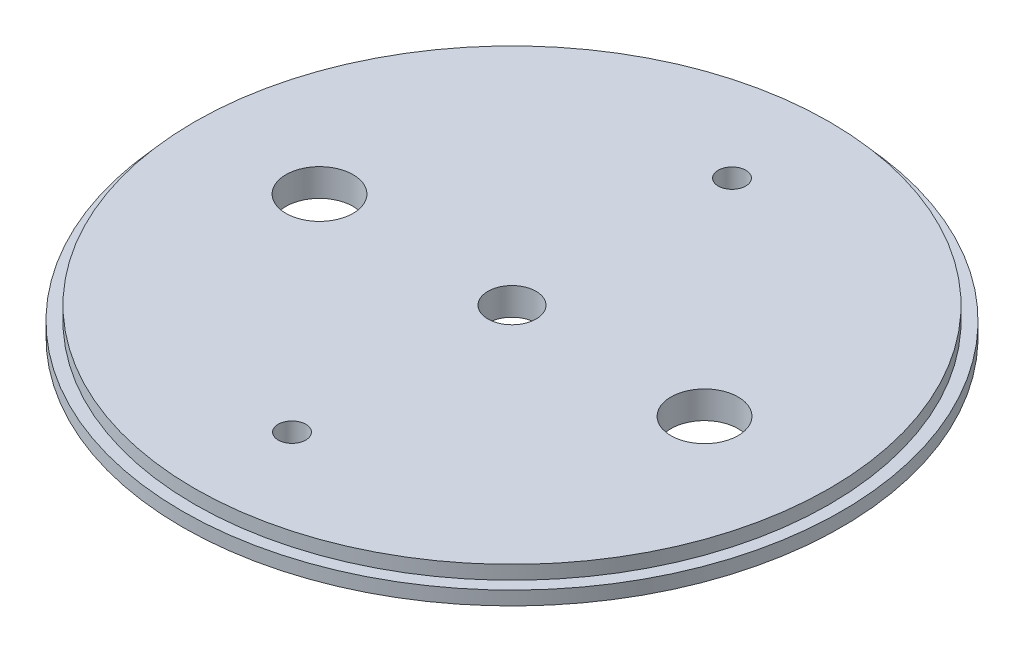
SolidWorks part; units mm, degrees
material "6061-T6 (SS)"
ref_plane "Front Plane" through (0, 0, 0) normal (0, 0, 1) x (1, 0, 0)
ref_plane "Top Plane" through (0, 0, 0) normal (0, 1, 0) x (1, 0, 0)
ref_plane "Right Plane" through (0, 0, 0) normal (1, 0, 0) x (0, 0, -1)
sketch "Sketch1" plane through (0, 0, 0) normal (0, 1, 0) x (1, 0, 0)
  circle A0 centre (0, 0) radius 73.3171
  circle A1 centre (0, 0) radius 76.0984
  dimension "D1" = 146.6342
  dimension "D2" = 152.1968
extrude "Boss-Extrude1" add sketch "Sketch1" along normal blind 3.175 contours A0 | A1 A0 region at (0, 0, 0) region at (-73.946, 0, 0)
extrude "Boss-Extrude2" add sketch "Sketch1<3>" along normal blind 6.35 contours A0 region at (0, 0, 0)
sketch "Sketch1<3>" plane through (0, 0, 0) normal (0, 1, 0) x (1, 0, 0) same geometry as "Sketch1"
sketch "Sketch3" plane through (0, 0, 0) normal (0, -1, 0) x (1, 0, 0)
  line L0 (44.45, 0) -> (-44.45, 0) construction
  line L1 (0, -50.8) -> (0, 50.8) construction
  circle A0 centre (0, 0) radius 5.5562
  circle A1 centre (-44.45, 0) radius 8.25
  circle A2 centre (44.45, 0) radius 8.25
  circle A3 centre (0, 50.8) radius 4.9609
  circle A4 centre (0, -50.8) radius 4.9609
  point P6 (0, 0)
  point P14 (0, 0)
  dimension "D1" = 11.1125
  dimension "D2" = 16.5001
  dimension "D3" = 9.9219
  dimension "D4" = 101.6
  dimension "D5" = 88.9
hole_wizard "1/4 (0.25) Diameter Hole1" positions "Sketch4" profile "Sketch5" hole size "1/4" standard "ANSI Inch" end condition through all
sketch "Sketch4" plane through (0, 0, 0) normal (0, -1, 0) x (-1, 0, 0)
  point P0 (0, 50.8)
  point P3 (0, -50.8)
sketch "Sketch5" plane through (0, 0, -50.8) normal (1, 0, 0) x (0, 0, -1)
  line L0 (0, 0) -> (0, 6.35)
  line L1 (0, 6.35) -> (3.175, 6.35)
  line L2 (3.175, 6.35) -> (3.175, 0)
  line L5 (3.175, 0) -> (0, 0)
  line L11 (0, -6.35) -> (0, 107.95) construction
  dimension "Thru Hole Dia." = 6.35
  dimension "Thru Hole Depth" = 6.35
extrude "Cut-Extrude1" [suppressed] cut sketch "Sketch3" against normal through all
hole_wizard "M18x2.5 Tapped Hole1" positions "Sketch6" profile "Sketch7" tap size "M18x2.5" standard "ANSI Metric" end condition through all
sketch "Sketch6" plane through (0, 0, 0) normal (0, -1, 0) x (-1, 0, 0)
  point P0 (44.45, 0)
  point P3 (-44.45, 0)
sketch "Sketch7" plane through (-44.45, 0, 0) normal (1, 0, 0) x (0, 0, -1)
  line L0 (0, 0) -> (0, 6.35)
  line L1 (0, 6.35) -> (7.75, 6.35)
  line L2 (7.75, 6.35) -> (7.75, 0)
  line L5 (7.75, 0) -> (0, 0)
  line L11 (0, -6.35) -> (0, 107.95) construction
  dimension "Thru Tap Drill Dia." = 15.5
  dimension "Thru Tap Drill Depth" = 6.35
cosmetic thread "Hole Thread1" parameters "D2"=18
cosmetic thread "Hole Thread2" parameters "D2"=18
extrude "Cut-Extrude2" cut sketch "Sketch3<3>" against normal through all contours A0
sketch "Sketch3<3>" plane through (0, 0, 0) normal (0, -1, 0) x (1, 0, 0) same geometry as "Sketch3"
